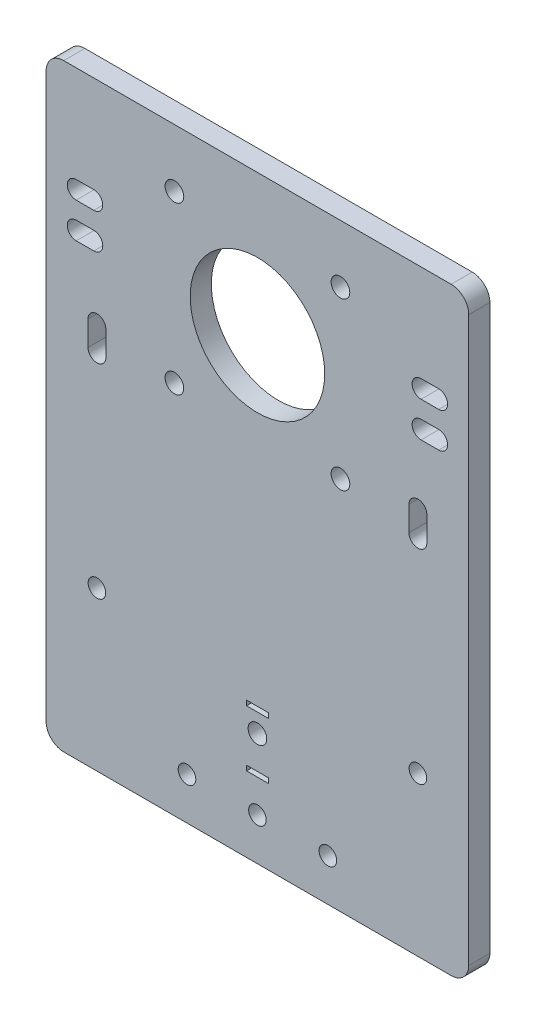
SolidWorks part; units mm, degrees
ref_plane "Front Plane" through (0, 0, 0) normal (0, 0, 1) x (1, 0, 0)
ref_plane "Top Plane" through (0, 0, 0) normal (0, 1, 0) x (1, 0, 0)
ref_plane "Right Plane" through (0, 0, 0) normal (1, 0, 0) x (0, 0, -1)
sketch "Sketch1" plane through (0, 0, 0) normal (0, 0, 1) x (1, 0, 0)
  line L1 (-55, -85) -> (55, -85)
  line L2 (-60, -80) -> (-60, 80)
  line L3 (-55, 85) -> (55, 85)
  line L4 (60, -80) -> (60, 80)
  line L5 (-60, -85) -> (60, 85) construction
  line L6 (-60, 85) -> (60, -85) construction
  arc A0 (-55, -85) -> (-60, -80) centre (-55, -80) cw
  arc A1 (55, -85) -> (60, -80) centre (55, -80) ccw
  arc A2 (55, 85) -> (60, 80) centre (55, 80) cw
  arc A3 (-60, 80) -> (-55, 85) centre (-55, 80) cw
  point P0 (0, 0)
  dimension "D3" = 5
  dimension "D1" = 170
  dimension "D2" = 120
extrude "Boss-Extrude1" add sketch "Sketch1" along normal blind 6
sketch "Sketch3" plane through (0, 0, 6) normal (0, 0, 1) x (1, 0, 0)
  line L0 (55, 85) -> (-55, 85) construction
  circle A0 centre (0, 45) radius 19.1
  point P6 (0, 85)
  dimension "D1" = 40
  dimension "D2" = 38.2
extrude "Cut-Extrude1" cut sketch "Sketch3" against normal blind 6
hole_wizard "M5 Clearance Hole1" positions "Sketch8" profile "Sketch9" hole size "M5" standard "ANSI Metric" end condition through all
sketch "Sketch8" plane through (0, 0, 6) normal (0, 0, 1) x (1, 0, 0)
  circle A0 centre (0, 45) radius 19.1 construction
  point P0 (-23.57, 68.57)
  point P2 (23.57, 68.57)
  point P4 (23.57, 21.43)
  point P6 (-23.57, 21.43)
  dimension "D2" = 23.57
  dimension "D3" = 23.57
  dimension "D4" = 23.57
  dimension "D5" = 23.57
  dimension "D1" = 23.57
sketch "Sketch9" plane through (-23.57, 68.57, 6) normal (1, 0, 0) x (0, -1, 0)
  line L0 (0, 0) -> (0, 6)
  line L1 (0, 6) -> (2.65, 6)
  line L2 (2.65, 6) -> (2.65, 0)
  line L5 (2.65, 0) -> (0, 0)
  line L11 (0, -6.35) -> (0, 107.95) construction
  dimension "Thru Hole Dia." = 5.3
  dimension "Thru Hole Depth" = 6
sketch "Sketch11" plane through (0, 0, 6) normal (0, 0, 1) x (1, 0, 0)
  line L0 (-45.57, 24.93) -> (-45.57, 17.93) construction
  line L1 (-43.03, 24.93) -> (-43.03, 17.93)
  line L2 (-48.11, 24.93) -> (-48.11, 17.93)
  line L5 (0, 63.1141) -> (0, -86.0691) construction
  line L8 (45.57, 24.93) -> (45.57, 17.93) construction
  line L9 (43.03, 24.93) -> (43.03, 17.93)
  line L10 (48.11, 24.93) -> (48.11, 17.93)
  arc A0 (-43.03, 24.93) -> (-48.11, 24.93) centre (-45.57, 24.93) ccw
  arc A1 (-48.11, 17.93) -> (-43.03, 17.93) centre (-45.57, 17.93) ccw
  circle A3 centre (-23.57, 21.43) radius 2.65 construction
  arc A4 (43.03, 24.93) -> (48.11, 24.93) centre (45.57, 24.93) cw
  arc A5 (48.11, 17.93) -> (43.03, 17.93) centre (45.57, 17.93) cw
  point P2 (-45.57, 21.43)
  point P15 (45.57, 21.43)
  dimension "D2" = 2.54
  dimension "D1" = 7
  dimension "D3" = 22
extrude "Cut-Extrude2" cut sketch "Sketch11" against normal blind 6
sketch "Sketch15" plane through (0, 0, 6) normal (0, 0, 1) x (1, 0, 0)
  line L0 (-51.46, 45) -> (-46.46, 45) construction
  line L1 (-51.46, 47.54) -> (-46.46, 47.54)
  line L2 (-51.46, 42.46) -> (-46.46, 42.46)
  line L3 (-51.46, 55) -> (-46.46, 55) construction
  line L4 (-51.46, 57.54) -> (-46.46, 57.54)
  line L5 (-51.46, 52.46) -> (-46.46, 52.46)
  line L6 (-60, 80) -> (-60, -80) construction
  line L8 (55, 85) -> (-55, 85) construction
  line L9 (0, 75.2932) -> (0, -13.323) construction
  line L10 (0, 63.1141) -> (0, -86.0691) construction
  line L11 (51.46, 45) -> (46.46, 45) construction
  line L12 (51.46, 47.54) -> (46.46, 47.54)
  line L13 (51.46, 42.46) -> (46.46, 42.46)
  line L14 (51.46, 55) -> (46.46, 55) construction
  line L15 (51.46, 57.54) -> (46.46, 57.54)
  line L16 (51.46, 52.46) -> (46.46, 52.46)
  arc A0 (-51.46, 47.54) -> (-51.46, 42.46) centre (-51.46, 45) ccw
  arc A1 (-46.46, 42.46) -> (-46.46, 47.54) centre (-46.46, 45) ccw
  arc A2 (-51.46, 57.54) -> (-51.46, 52.46) centre (-51.46, 55) ccw
  arc A3 (-46.46, 52.46) -> (-46.46, 57.54) centre (-46.46, 55) ccw
  arc A5 (51.46, 47.54) -> (51.46, 42.46) centre (51.46, 45) cw
  arc A6 (46.46, 42.46) -> (46.46, 47.54) centre (46.46, 45) cw
  arc A7 (51.46, 57.54) -> (51.46, 52.46) centre (51.46, 55) cw
  arc A8 (46.46, 52.46) -> (46.46, 57.54) centre (46.46, 55) cw
  point P2 (-48.96, 45)
  point P7 (-48.96, 55)
  point P15 (-54, 45)
  point P32 (48.96, 45)
  point P39 (48.96, 55)
  dimension "D1" = 30
  dimension "D2" = 2.54
  dimension "D4" = 5
  dimension "D5" = 6
  dimension "D6" = 10
extrude "Cut-Extrude4" cut sketch "Sketch15" against normal blind 6
hole_wizard "Ø5.0 (5) Diameter Hole4" positions "Sketch17" profile "Sketch18" hole size "Ø5.0" standard "ANSI Metric" end condition through all
sketch "Sketch17" plane through (0, 0, 6) normal (0, 0, 1) x (1, 0, 0)
  line L1 (-55, -85) -> (55, -85) construction
  line L2 (60, -80) -> (60, 80) construction
  line L3 (-60, 80) -> (-60, -80) construction
  point P0 (-45.57, -39.97)
  point P2 (45.57, -39.97)
  point P4 (20, -73)
  point P6 (0, -73)
  point P8 (-20, -73)
  dimension "D3" = 40
  dimension "D1" = 61.4
  dimension "D2" = 12
  dimension "D4" = 40
sketch "Sketch18" plane through (-45.57, -39.97, 6) normal (1, 0, 0) x (0, -1, 0)
  line L0 (0, 0) -> (0, 6)
  line L1 (0, 6) -> (2.5, 6)
  line L2 (2.5, 6) -> (2.5, 0)
  line L5 (2.5, 0) -> (0, 0)
  line L11 (0, -6.35) -> (0, 107.95) construction
  dimension "Thru Hole Dia." = 5
  dimension "Thru Hole Depth" = 6
hole_wizard "M5 Clearance Hole2" positions "Sketch19" profile "Sketch20" hole size "M5" standard "ANSI Metric"
sketch "Sketch19" plane through (0, 0, 0) normal (0, 0, -1) x (-1, 0, 0)
  circle A0 centre (0, -73) radius 2.5 construction
  point P0 (0, -53)
  dimension "D1" = 20
sketch "Sketch20" plane through (0, -53, 0) normal (1, 0, 0) x (0, 1, 0)
  line L0 (0, 0) -> (0, 11.5923)
  line L1 (0, 11.5923) -> (2.65, 10)
  line L2 (2.65, 10) -> (2.65, 0)
  line L5 (2.65, 0) -> (0, 0)
  line L10 (0, 11.5923) -> (-2.65, 10) construction
  line L11 (0, -6.35) -> (0, 107.95) construction
  dimension "Hole Dia." = 5.3
  dimension "Hole Depth" = 10
  dimension "Drill Angle" = 118
sketch "Sketch21" plane through (0, 0, 0) normal (0, 0, -1) x (-1, 0, 0)
  line L1 (-3.1, -46.3) -> (3.1, -46.3)
  line L2 (-3.1, -46.3) -> (-3.1, -47.7)
  line L3 (-3.1, -47.7) -> (3.1, -47.7)
  line L4 (3.1, -46.3) -> (3.1, -47.7)
  line L5 (-3.1, -46.3) -> (3.1, -47.7) construction
  line L6 (-3.1, -47.7) -> (3.1, -46.3) construction
  circle A0 centre (0, -53) radius 2.65 construction
  point P0 (0, -47)
  dimension "D1" = 6.2
  dimension "D2" = 1.4
  dimension "D3" = 6
extrude "Cut-Extrude5" cut sketch "Sketch21" against normal blind 6
sketch "Sketch22" plane through (0, 0, 6) normal (0, 0, 1) x (1, 0, 0)
  line L1 (-3.1, -63.7) -> (3.1, -63.7)
  line L2 (-3.1, -63.7) -> (-3.1, -62.3)
  line L3 (-3.1, -62.3) -> (3.1, -62.3)
  line L4 (3.1, -63.7) -> (3.1, -62.3)
  line L5 (-3.1, -63.7) -> (3.1, -62.3) construction
  line L6 (-3.1, -62.3) -> (3.1, -63.7) construction
  circle A0 centre (0, -53) radius 2.65 construction
  point P0 (0, -63)
  dimension "D1" = 6.2
  dimension "D2" = 1.4
  dimension "D3" = 10
extrude "Cut-Extrude6" cut sketch "Sketch22" against normal blind 10
